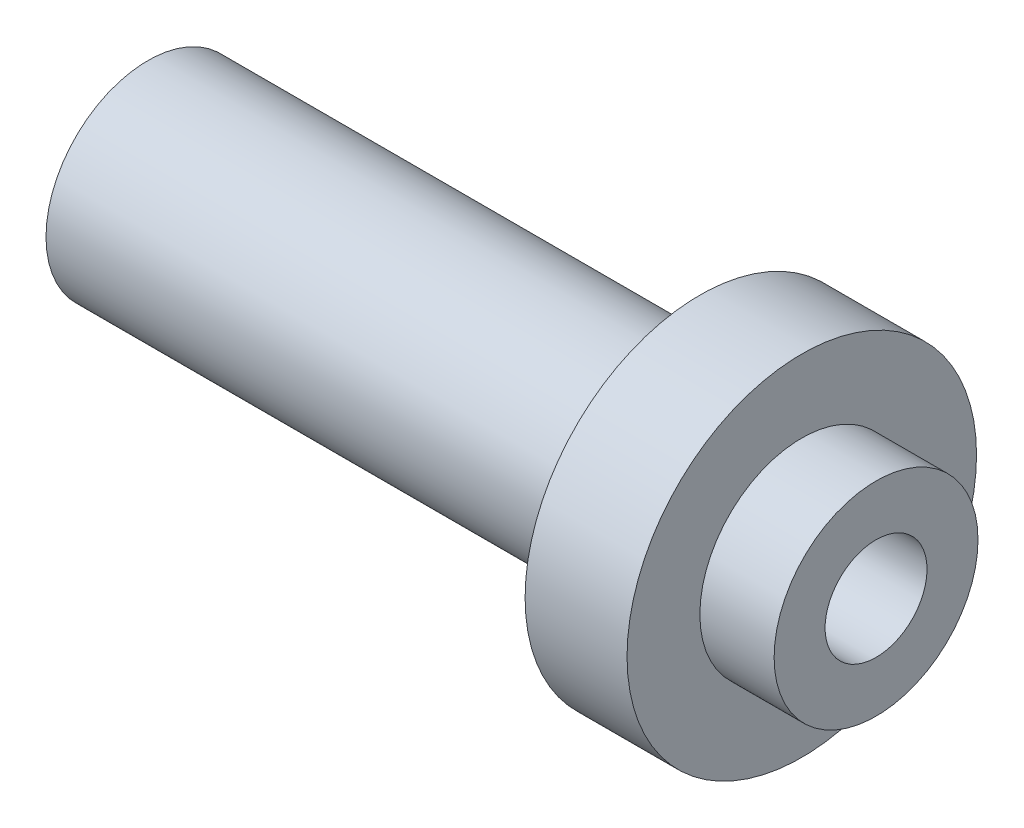
SolidWorks part; units mm, degrees
ref_plane "Front Plane" through (0, 0, 0) normal (0, 0, 1) x (1, 0, 0)
ref_plane "Top Plane" through (0, 0, 0) normal (0, 1, 0) x (1, 0, 0)
ref_plane "Right Plane" through (0, 0, 0) normal (1, 0, 0) x (0, 0, -1)
sketch "Sketch1" plane through (0, 0, 0) normal (0, 0, 1) x (1, 0, 0)
  line L0 (-5.1, 12) -> (-5.1, 7)
  line L1 (-5.1, 12) -> (-12.1, 12)
  line L2 (-12.1, 12) -> (-12.1, 7)
  line L3 (-12.1, 7) -> (-50, 7)
  line L4 (-50, 7) -> (-50, 0)
  line L5 (-78.3439, 0) -> (16.242, 0) construction
  line L6 (-5.1, 7) -> (0, 7)
  line L7 (0, 7) -> (0, 0)
  line L8 (-50, 0) -> (0, 0)
  dimension "D1" = 7
  dimension "D2" = 7
  dimension "D3" = 5
  dimension "D4" = 5.1
  dimension "D5" = 7
  dimension "D6" = 50
  dimension "D8" = 7
revolve "Revolve1" add sketch "Sketch1" angle 360 about L5
sketch "Sketch2" plane through (0, 0, 0) normal (1, 0, 0) x (0, 0, -1)
  circle A0 centre (0, 0) radius 3.5
  dimension "D1" = 7
ref_axis "Axis1" through (-5.1, 0, 0) along (-1, 0, 0)
ref_plane "Plane1" through (0, 12, 0) normal (0, 1, 0) x (1, 0, 0)
ref_plane "Plane2" through (0, 0, 12) normal (0, 0, 1) x (1, 0, 0)
hole_wizard "Trou taraudé M8x1.01" positions "Esquisse1" profile "Esquisse3" tap size "M8x1.0" standard "ISO"
sketch "Esquisse1" plane through (0, 0, 0) normal (1, 0, 0) x (0, 0, -1)
  point P0 (0, 0)
sketch "Esquisse3" plane through (0, 0, 0) normal (0, 1, 0) x (0, 0, -1)
  line L0 (0, 0) -> (0, 32.103)
  line L1 (0, 32.103) -> (3.5, 30)
  line L2 (3.5, 30) -> (3.5, 0)
  line L5 (3.5, 0) -> (0, 0)
  line L10 (0, 32.103) -> (-3.5, 30) construction
  line L11 (0, -6.35) -> (0, 107.95) construction
  dimension "Diamètre du trou pour taraudage" = 7
  dimension "Profondeur du trou pour taraudage" = 30
  dimension "Angle de pointe" = 118
cosmetic thread "Filetage de perçage1" parameters "D1"=25, "D2"=8
move or copy body "Body-Move/Copy1" [suppressed] bodies to move or copy 111
